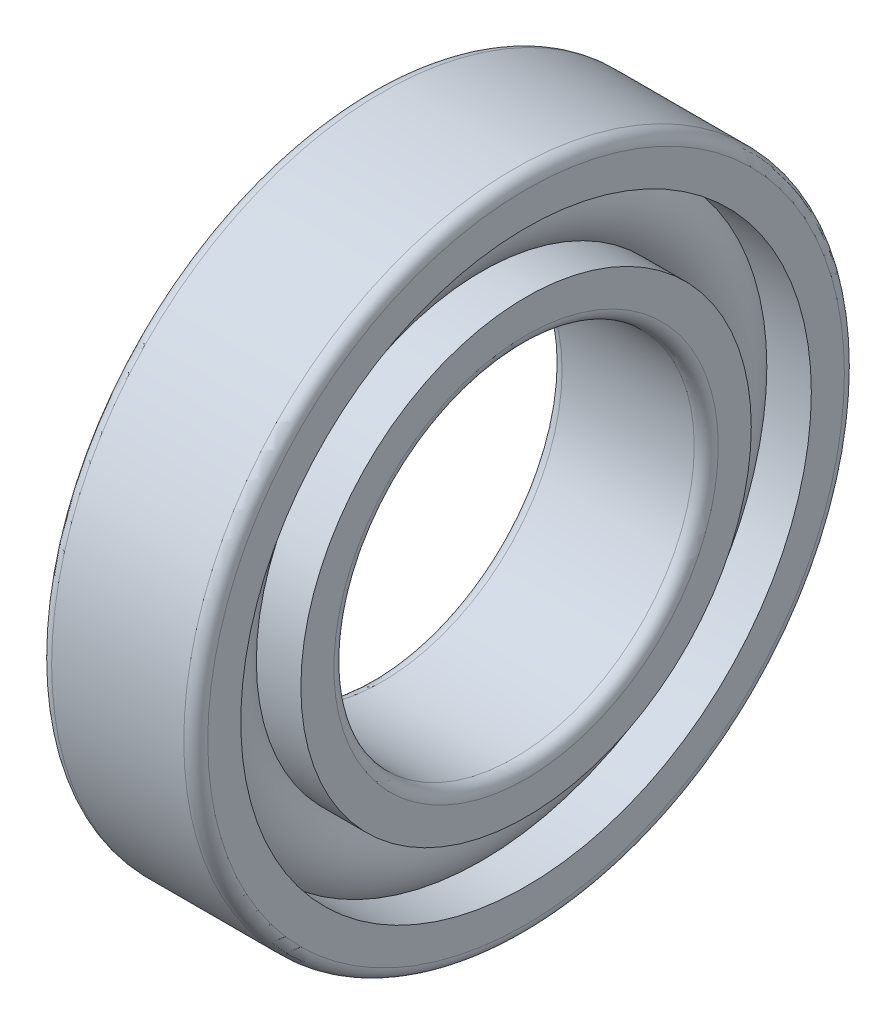
SolidWorks part; units mm, degrees
ref_plane "Plane1" through (0, 0, 0) normal (0, 0, 1) x (1, 0, 0)
ref_plane "Plane2" through (0, 0, 0) normal (0, 1, 0) x (1, 0, 0)
ref_plane "Plane3" through (0, 0, 0) normal (1, 0, 0) x (0, 0, -1)
other "Configuration Table"
sketch "Clipboard" plane through (0, 0, 0) normal (0, 0, 1) x (1, 0, 0)
  line L0 (-10, 0) -> (10, 0) construction
  line L1 (0, 0) -> (22.3471, -0.7804)
  line L2 (0, 0) -> (21.2371, 0.7416)
  line L3 (0, 0) -> (22.3471, -0.7804)
  line L4 (0, 0) -> (-22.3573, -0.3902)
  dimension "BallCLRad" = 21.25
sketch "CagSpiSke" plane through (0, 0, 0) normal (0, 0, 1) x (1, 0, 0)
  line L0 (0.375, 20.625) -> (0.375, 21.875)
  line L1 (0.375, 21.875) -> (-0.375, 21.875)
  line L2 (-0.375, 21.875) -> (-0.375, 20.625)
  line L3 (-0.375, 20.625) -> (0.375, 20.625)
  line L4 (-20.6375, 0) -> (20.6375, 0) construction
  line L5 (0, 0) -> (0, 23.7692) construction
  dimension "OD" = 43.75
  dimension "ID" = 41.25
revolve "CageSpine" add sketch "CagSpiSke" angle 0.001 about L4 reverse direction yes
ref_axis "Axis1" through (-50, 0, 0) along (1, 0, 0)
sketch "CagBalSke" plane through (0, 0, 0) normal (0, 0, 1) x (1, 0, 0)
  line L0 (-4.125, 21.25) -> (4.125, 21.25)
  line L1 (-1.905, 21.25) -> (1.905, 21.25) construction
  line L2 (-10, 0) -> (10, 0) construction
  line L3 (0, 0) -> (0, 24) construction
  arc A0 (4.125, 21.25) -> (-4.125, 21.25) centre (0, 21.25) cw
  dimension "BallCLRad" = 21.25
revolve "CageBall" [suppressed] add sketch "CagBalSke" angle 360 about L1 reverse direction yes
pattern_circular "CageBalls" [suppressed] count 2 every 180 about axis through (-50, 0, 0) along (1, 0, 0)
sketch "CagTrmODSke" plane through (0, 0, 0) normal (0, 0, 1) x (1, 0, 0)
  line L0 (4.126, 21.875) -> (4.126, 25.376)
  line L1 (4.126, 25.376) -> (-4.126, 25.376)
  line L2 (-4.126, 25.376) -> (-4.126, 21.875)
  line L3 (-4.126, 21.875) -> (4.126, 21.875)
  line L4 (-20.6375, 0) -> (20.6375, 0) construction
  line L5 (0, 0) -> (0, 25) construction
  dimension "Width" = 8.252
  dimension "ID" = 43.75
  dimension "OD" = 50.752
revolve "CageTrimOD" [suppressed] cut sketch "CagTrmODSke" angle 360 about L4 reverse direction yes
sketch "CagTrmIDSke" plane through (0, 0, 0) normal (0, 0, 1) x (1, 0, 0)
  line L0 (4.126, 17.126) -> (4.126, 20.625)
  line L1 (4.126, 20.625) -> (-4.126, 20.625)
  line L2 (-4.126, 20.625) -> (-4.126, 17.126)
  line L3 (-4.126, 17.126) -> (4.126, 17.126)
  line L4 (-20.6375, 0) -> (20.6375, 0) construction
  line L5 (0, 0) -> (0, 25) construction
  dimension "Width" = 8.252
  dimension "ID" = 34.252
  dimension "OD" = 41.25
revolve "CageTrimID" [suppressed] cut sketch "CagTrmIDSke" angle 360 about L4 reverse direction yes
sketch "BalSimSke" plane through (0, 0, 0) normal (0, 0, 1) x (1, 0, 0)
  line L0 (-10, 0) -> (10, 0) construction
  line L1 (-10, 21.25) -> (10, 21.25) construction
  line L2 (0, 0) -> (0, 23) construction
  circle A0 centre (0, 21.25) radius 3.75
  dimension "BallCLRad" = 21.25
  dimension "Ball_diameter" = 7.5
revolve "BallsSimplified" add sketch "BalSimSke" angle 360 about L0
sketch "BalDetSke" plane through (0, 0, 0) normal (0, 0, 1) x (1, 0, 0)
  line L0 (-3.75, 21.25) -> (3.75, 21.25)
  line L1 (-1.905, 21.25) -> (1.905, 21.25) construction
  line L2 (0, 0) -> (0, 25) construction
  arc A0 (3.75, 21.25) -> (-3.75, 21.25) centre (0, 21.25) cw
  dimension "BallCLRad" = 21.25
  dimension "Ball_diameter" = 7.5
revolve "BallDetailed" [suppressed] add sketch "BalDetSke" angle 360 about L1 reverse direction yes
sketch "InnRacSke" plane through (0, 0, 0) normal (0, 0, 1) x (1, 0, 0)
  line L0 (-2.7615, 18.75) -> (-6.5, 18.75)
  line L1 (-6.5, 18.75) -> (-6.5, 16)
  line L2 (-5.5, 15) -> (5.5, 15)
  line L3 (6.5, 16) -> (6.5, 18.75)
  line L4 (6.5, 18.75) -> (2.7615, 18.75)
  line L5 (-20.6375, 0) -> (20.6375, 0) construction
  line L6 (0, 0) -> (0, 30) construction
  arc A0 (-6.5, 16) -> (-5.5, 15) centre (-5.5, 16) ccw
  arc A1 (5.5, 15) -> (6.5, 16) centre (5.5, 16) ccw
  arc A2 (2.7615, 18.75) -> (-2.7615, 18.75) centre (0, 21.25) cw
  dimension "BallCLRad" = 21.25
  dimension "Fillet_radius" = 1
  dimension "Ball_diameter" = 7.45
  dimension "ID" = 30
  dimension "OD" = 37.5
  dimension "Width" = 13
revolve "InnerRace" add sketch "InnRacSke" angle 360 about L5 reverse direction yes
sketch "OutRacSke" plane through (0, 0, 0) normal (0, 0, 1) x (1, 0, 0)
  line L0 (-2.7615, 23.75) -> (-6.5, 23.75)
  line L1 (-6.5, 23.75) -> (-6.5, 26.5)
  line L2 (-5.5, 27.5) -> (5.5, 27.5)
  line L3 (6.5, 26.5) -> (6.5, 23.75)
  line L4 (6.5, 23.75) -> (2.7615, 23.75)
  line L5 (-20.6375, 0) -> (20.6375, 0) construction
  line L6 (0, 0) -> (0, 30) construction
  arc A0 (-6.5, 26.5) -> (-5.5, 27.5) centre (-5.5, 26.5) cw
  arc A1 (5.5, 27.5) -> (6.5, 26.5) centre (5.5, 26.5) cw
  arc A2 (2.7615, 23.75) -> (-2.7615, 23.75) centre (0, 21.25) ccw
  dimension "BallCLRad" = 21.25
  dimension "Fillet_radius" = 1
  dimension "Ball_diameter" = 7.45
  dimension "Width" = 13
revolve "OuterRace" add sketch "OutRacSke" angle 360 about L5 reverse direction yes
pattern_circular "BallsDetailed" [suppressed] count 2 every 180 about axis through (-50, 0, 0) along (1, 0, 0)
equation "\"BallCLRad@Clipboard\" = ( \"OD@OutRacSke\" + \"ID@InnRacSke\" ) / 4"
equation "\"BallCLRad@BalSimSke\" = \"BallCLRad@Clipboard\""
equation "\"BallCLRad@BalDetSke\" = \"BallCLRad@Clipboard\""
equation "\"BallCLRad@InnRacSke\" = \"BallCLRad@Clipboard\""
equation "\"BallCLRad@OutRacSke\" = \"BallCLRad@Clipboard\""
equation "\"Ball_diameter@InnRacSke\" = \"Ball_diameter@BalDetSke\" - 0.05"
equation "\"Ball_diameter@OutRacSke\" = \"Ball_diameter@BalDetSke\" - 0.05"
equation "\"Ball_diameter@BalSimSke\" = \"Ball_diameter@BalDetSke\""
equation "\"Width@OutRacSke\" = \"Width@InnRacSke\""
equation "\"Fillet_radius@OutRacSke\" = \"Fillet_radius@InnRacSke\""
equation "\"Max_count@Clipboard\" = int( 3.14159265 / atn(( \"Ball_diameter@BalDetSke\" / 2) / sqr( \"BallCLRad@Clipboard\"  *  \"BallCLRad@Clipboard\" - ( \"Ball_diameter@BalDetSke\" / 2) *  ( \"Ball_diameter@BalDetSke\" / 2))))"
equation "\"Max_count@Clipboard\" = ((sgn( \"Max_count@Clipboard\" - \"Count@Clipboard\" )-1)*( \"Max_count@Clipboard\" - \"Count@Clipboard\" ))/-2+ \"Count@Clipboard\""
equation "\"Count@BallsDetailed\" = int( \"Show_count@Clipboard\" ) "
equation "\"Count@BallsDetailed\" = ((sgn( \"Count@BallsDetailed\" - \"Max_count@Clipboard\" )-1)*( \"Count@BallsDetailed\" - \"Max_count@Clipboard\" ))/-2+ \"Max_count@Clipboard\""
equation "\"Count@BallsDetailed\" = ((sgn( \"Count@BallsDetailed\" - \"Min_count@Clipboard\" )+1)*( \"Count@BallsDetailed\" - \"Min_count@Clipboard\"))/2 +\"Min_count@Clipboard\""
equation "\"Angle@BallsDetailed\" = 360.0 / \"Max_count@Clipboard\""
equation "\"BallCLRad@CagBalSke\" = \"BallCLRad@Clipboard\""
equation "\"Count@CageBalls\" = \"Count@BallsDetailed\""
equation "\"Angle@CageBalls\" = \"Angle@BallsDetailed\""
equation "\"Angle@CageSpine\" =  \"Angle@CageBalls\" * ( \"Count@CageBalls\" -1 + int( \"Count@CageBalls\" / \"Max_count@Clipboard\" ) )  + 0.001 -  int( \"Count@CageBalls\" / \"Max_count@Clipboard\" ) * 0.001"
equation "\"Angle@CageSpine\" =  \"Angle@CageSpine\" * int( \"Min_count@Clipboard\" / 2) + int(1 / \"Min_count@Clipboard\")  * 0.001"
equation "\"CageWallOD@CagBalSke\" =  \"Ball_diameter@BalDetSke\" * 1.1"
equation "\"Thickness@CagSpiSke\" =  \"Ball_diameter@BalDetSke\" * 0.1"
equation "\"OD@CagTrmODSke\" = \"BallCLRad@Clipboard\" * 2 + \"CageWallOD@CagBalSke\" + 0.002"
equation "\"ID@CagTrmODSke\" = \"BallCLRad@Clipboard\" * 2 + \"Ball_diameter@BalDetSke\" / 6"
equation "\"OD@CagTrmIDSke\" = \"BallCLRad@Clipboard\" * 2 - \"Ball_diameter@BalDetSke\" / 6"
equation "\"ID@CagTrmIDSke\" = \"BallCLRad@Clipboard\" * 2 - \"CageWallOD@CagBalSke\" + 0.002"
equation "\"OD@CagSpiSke\" = \"ID@CagTrmODSke\""
equation "\"ID@CagSpiSke\" = \"OD@CagTrmIDSke\""
equation "\"Width@CagTrmODSke\" = \"CageWallOD@CagBalSke\" + 0.002"
equation "\"Width@CagTrmIDSke\" = \"CageWallOD@CagBalSke\" + 0.002"
